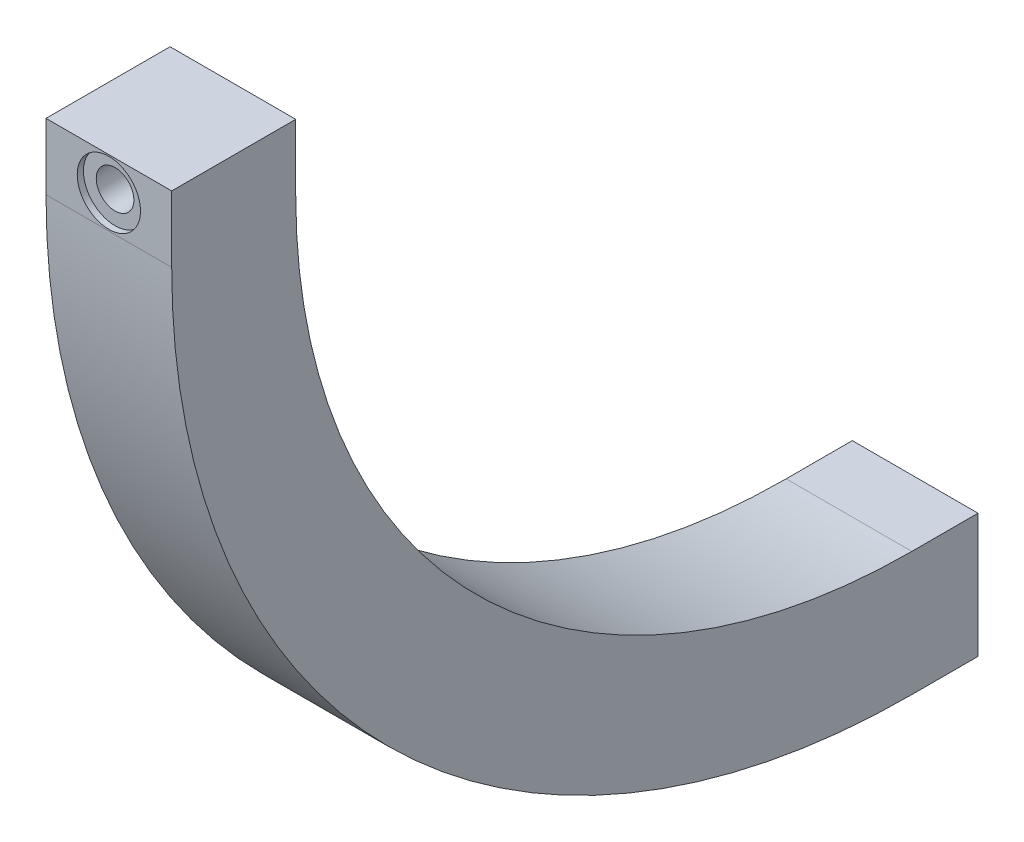
SolidWorks part; units mm, degrees
ref_plane "Front Plane" through (0, 0, 0) normal (0, 0, 1) x (1, 0, 0)
ref_plane "Top Plane" through (0, 0, 0) normal (0, 1, 0) x (1, 0, 0)
ref_plane "Right Plane" through (0, 0, 0) normal (1, 0, 0) x (0, 0, -1)
ref_axis "Z" through (0, 0, 22.75) along (0, 0, -1)
sketch "Sketch4" plane through (0, 0, 0) normal (0, 0, 1) x (1, 0, 0)
  circle A0 centre (0, 0) radius 77.5 construction
  dimension "D1" = 155
sketch "Sketch5" plane through (0, 0, 0) normal (1, 0, 0) x (0, 0, -1)
  line L0 (-78.5, 4) -> (-78.5, 0)
  line L1 (-78.5, 0) -> (-78.5, -4)
  line L2 (-93.5, -4) -> (-93.5, 4)
  line L6 (-93.5, 4) -> (-78.5, 4)
  line L12 (-22.75, 0) -> (-13.0351, 0) construction
  line L13 (0, 0) -> (-14.9091, -14.9091) construction
  line L14 (0, 0) -> (7.0065, 0) construction
  line L15 (0, -78.5) -> (-4, -78.5)
  line L16 (4, -78.5) -> (0, -78.5)
  line L17 (-4, -93.5) -> (4, -93.5)
  line L18 (4, -93.5) -> (4, -78.5)
  circle A0 centre (0, 0) radius 14 construction
  arc A1 (-78.5, -4) -> (-4, -78.5) centre (-4, -4) ccw
  arc A2 (-93.5, -4) -> (-4, -93.5) centre (-4, -4) ccw
  point P2 (9.4307, -21)
  point P4 (0, -2.1363)
  dimension "D1" = 28
  dimension "D4" = 4
  dimension "D2" = 45
  dimension "D3" = 15
  dimension "D5" = 78.5
sketch "Sketch6" plane through (0, 0, 0) normal (0, 1, 0) x (1, 0, 0)
  circle A0 centre (0, 0) radius 77.5 construction
  dimension "D1" = 155
extrude "Boss-Extrude1" add sketch "Sketch5" along normal blind 7.6 and the other way blind 7.6
sketch "Sketch7" plane through (0, 0, 0) normal (0, 0, 1) x (1, 0, 0)
  circle A0 centre (0, 0) radius 1.75
  dimension "D1" = 3.5
extrude "Cut-Extrude1" cut sketch "Sketch7" along normal through all
ref_axis "Y" through (0, -9.3489, 0) along (0, -1, 0)
sketch "Sketch12" plane through (0, 0, 93.5) normal (0, 0, 1) x (1, 0, 0)
  circle A0 centre (0, 0) radius 2.275
  dimension "D1" = 4.55
extrude "Cut-Extrude7" cut sketch "Sketch12" against normal blind 6
sketch "Sketch14" plane through (0, 0, 93.5) normal (0, 0, -1) x (1, 0, 0)
  circle A0 centre (0, 0) radius 3.825
  dimension "D1" = 7.65
extrude "Cut-Extrude10" cut sketch "Sketch14" along normal blind 0.75
sketch "Sketch16" plane through (0, 0, 0) normal (1, 0, 0) x (0, 0, -1)
  line L0 (0, -92.5) -> (0, 0) construction
  dimension "D1" = 92.5
ref_plane "Plane1" through (0, -92.5, 0) normal (0, 1, 0) x (1, 0, 0)
ref_axis "CX" through (0, -92.5, 4.4) along (0, 0, -1)
ref_plane "Plane2" through (0, 0, 0) normal (0, 0, -1) x (0, 1, 0)
ref_plane "Plane3" through (0, 0, 0) normal (1, 0, 0) x (0, 0, -1)
ref_axis "CZ" through (0, -8.7018, 0) along (0, -1, 0)
ref_axis "CY" through (-0.6471, -92.5, 0) along (1, 0, 0)
ref_point "CO"
sketch "Sketch15" plane through (0, -93.5, 0) normal (0, -1, 0) x (1, 0, 0)
  circle A0 centre (0, 0) radius 1.5
  dimension "D1" = 3
extrude "Cut-Extrude11" cut sketch "Sketch15" against normal blind 6
equation "\"rbracket-width\"= \"L2Thickness\" + 0.2"
equation "\"EyeCaptureRadius\"= ( \"EyeDiameter\" + \"EyeClearance\" ) / 2"
equation "\"rbracket_planetocenterline_dist\"= \"BasePlaneDistance\""
equation "\"EyeDiameter\" = 155"
equation "\"BasePlaneDistance\" = \"EyeDiameter\"/2+15"
equation "\"EyeClearance\" = 2"
equation "\"D1@Sketch4\"=\"EyeDiameter\""
equation "\"D1@Sketch6\"=\"EyeDiameter\""
equation "\"D1@Boss-Extrude1\"=\"rbracket-width\"/2"
equation "\"D2@Boss-Extrude1\"=\"rbracket-width\"/2"
equation "\"L2Thickness\" = 15"
equation "\"D3@Sketch5\"=\"L2Thickness\""
equation "\"D5@Sketch5\"=(\"EyeDiameter\"+\"EyeClearance\")/2"
equation "\"BearingThickness\"= 6"
equation "\"BearingOD\"=4.5"
equation "\"OuterBearingProudDistance\"= 0"
equation "\"D1@Cut-Extrude7\"=\"BearingThickness\"-\"OuterBearingProudDistance\""
equation "\"D1@Sketch12\"= \"BearingOD\" + \"PrinterFilamentThickness\" *\"ApplyPrinterOffset\" / 2"
equation "\"FlangeOD\"=7.5"
equation "\"FlangeThickness\"= 0.75"
equation "\"D1@Sketch14\"=\"FlangeOD\" + \"PrinterFilamentThickness\"*1.5 * \"ApplyPrinterOffset\""
equation "\"D1@Cut-Extrude10\"=\"FlangeThickness\""
equation "\"PrinterFilamentThickness\"= 0.1'For setting distances for things like pressfits"
equation "\"ApplyPrinterOffset\"= 1'Set to 0 for line-to-line. Set to 1 for applying guestimate dimensions to make the printer produce good parts"
equation "\"D1@Cut-Extrude11\"=3*1.5"
equation "\"D1@Sketch16\"=\"BasePlaneDistance\""
